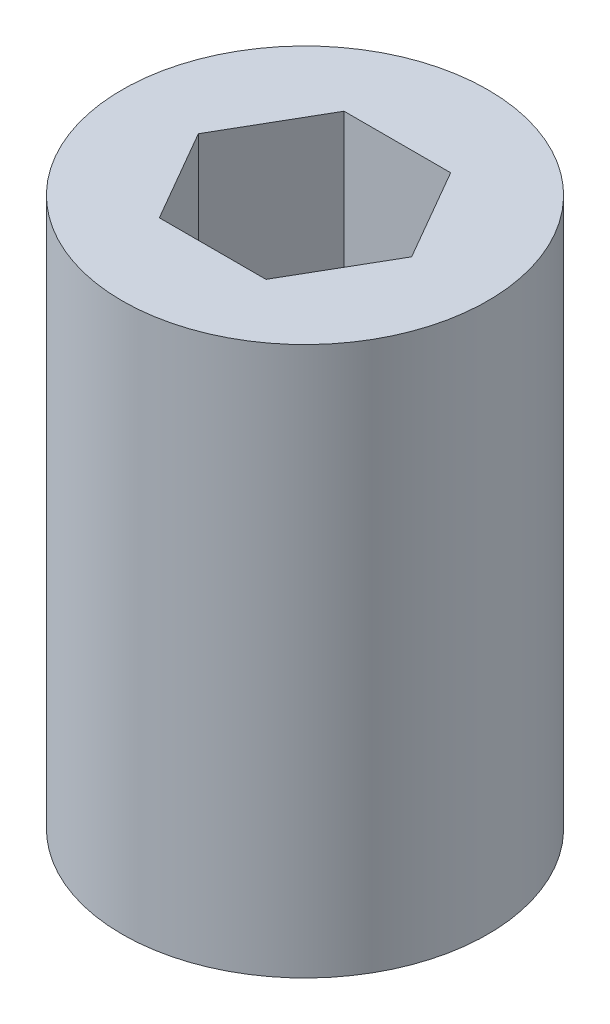
SolidWorks part; units mm, degrees
ref_plane "Front Plane" through (0, 0, 0) normal (0, 0, 1) x (1, 0, 0)
ref_plane "Top Plane" through (0, 0, 0) normal (0, 1, 0) x (1, 0, 0)
ref_plane "Right Plane" through (0, 0, 0) normal (1, 0, 0) x (0, 0, -1)
sketch "Sketch1" plane through (0, 0, 0) normal (0, 1, 0) x (1, 0, 0)
  circle A0 centre (0, 0) radius 12.7
  dimension "D1" = 25.4
extrude "Boss-Extrude1" add sketch "Sketch1" along normal blind 38.1
sketch "Sketch2" plane through (0, 38.1, 0) normal (0, 1, 0) x (1, 0, 0)
  circle A0 centre (0, 0) radius 12.7
extrude "Boss-Extrude2" [suppressed] add sketch "Sketch2" against normal blind 50.8 draft 5 draft outward yes
sketch "Sketch3" plane through (0, 0, 0) normal (0, -1, 0) x (-1, 0, 0)
  circle A0 centre (0, 0) radius 12.7
extrude "Boss-Extrude3" [suppressed] add sketch "Sketch3" against normal blind 50.8 draft 5 draft outward yes
sketch "Sketch5" plane through (0, 0, 0) normal (0, -1, 0) x (-1, 0, 0)
  line L1 (-7.4057, 0) -> (-3.7028, -6.4135)
  line L2 (-3.7028, -6.4135) -> (3.7028, -6.4135)
  line L3 (3.7028, -6.4135) -> (7.4057, 0)
  line L4 (7.4057, 0) -> (3.7028, 6.4135)
  line L5 (3.7028, 6.4135) -> (-3.7028, 6.4135)
  line L6 (-3.7028, 6.4135) -> (-7.4057, 0)
  circle A0 centre (0, 0) radius 6.4135 construction
  dimension "D1" = 12.827
extrude "Cut-Extrude1" cut sketch "Sketch5" against normal through all
